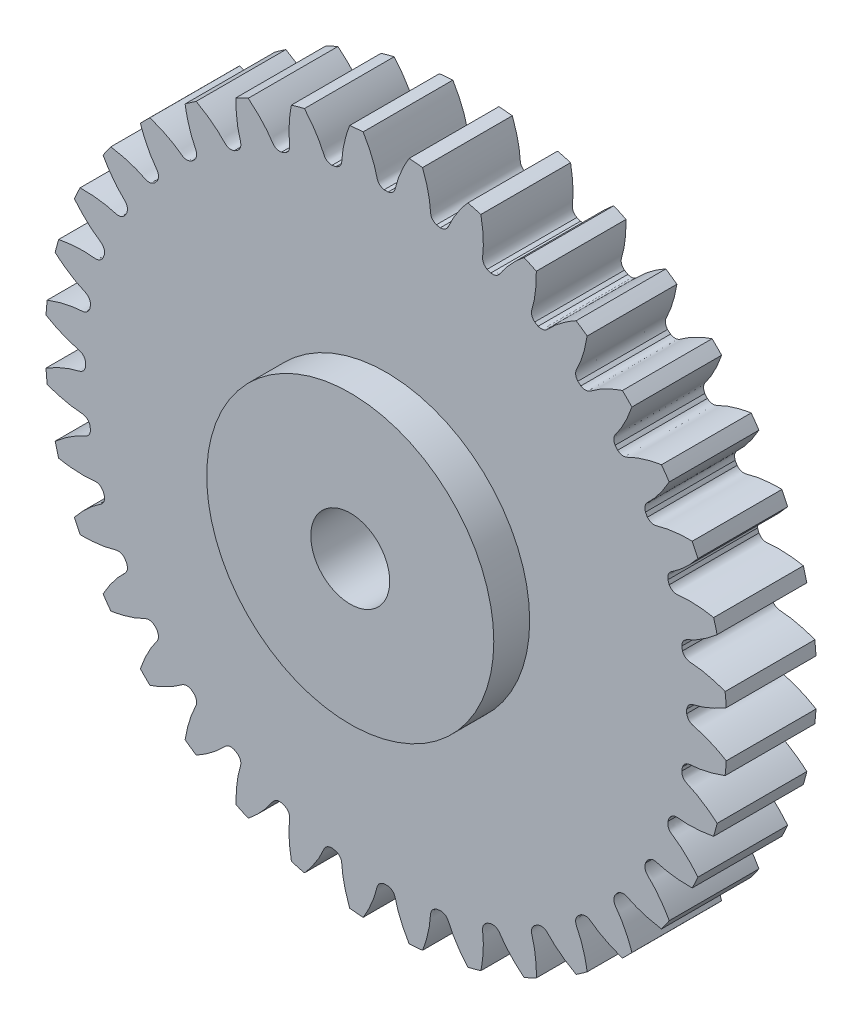
SolidWorks part; units mm, degrees
ref_plane "前视基准面" through (0, 0, 0) normal (0, 0, 1) x (1, 0, 0)
ref_plane "上视基准面" through (0, 0, 0) normal (0, 1, 0) x (1, 0, 0)
ref_plane "右视基准面" through (0, 0, 0) normal (1, 0, 0) x (0, 0, -1)
other "Configuration Table"
sketch "草图1" plane through (0, 0, 0) normal (0, 0, 1) x (1, 0, 0)
  circle A0 centre (0, 0) radius 9.5
extrude "凸台-拉伸1" add sketch "草图1" along normal blind 2.5
ref_axis "基准轴1" through (0, 0, 2.5) along (0, 0, -1)
sketch "草图2" plane through (0, 0, 0) normal (0, 0, 1) x (1, 0, 0)
  line L0 (0, 0) -> (0, 9.5) construction
  circle A0 centre (0, 0) radius 9.5 construction
  arc A1 (0.0549, 8.3748) -> (-0.0549, 8.3748) centre (0, 0) ccw
  arc A2 (1.757, 10.7884) -> (-1.757, 10.7884) centre (0, 0) ccw
  spline S0 degree 3 poles (0.0549, 8.3748) (0.235, 8.4152) (0.2505, 8.5493) (0.2882, 8.6914) (0.2997, 8.7319) (0.3131, 8.7753) (0.3284, 8.8217) (0.3457, 8.871) (0.3652, 8.9231) (0.3869, 8.9779) (0.4111, 9.0354) (0.4378, 9.0956) (0.4671, 9.1582) (0.4992, 9.2232) (0.5341, 9.2907) (0.5719, 9.3603) (0.6128, 9.4322) (0.6569, 9.5061) (0.7043, 9.582) (0.755, 9.6598) (0.8091, 9.7393) (0.8668, 9.8205) (0.9281, 9.9032) (0.9931, 9.9874) (1.0619, 10.0729) (1.1346, 10.1596) (1.2112, 10.2474) (1.2919, 10.3361) (1.3766, 10.4256) (1.4655, 10.5159) (1.5912, 10.6386) (1.6895, 10.7288) (1.757, 10.7884) knots 0 0 0 0 0.120371 0.133303 0.147364 0.162556 0.178878 0.19633 0.214913 0.234626 0.255469 0.277443 0.300547 0.324782 0.350146 0.376641 0.404267 0.433023 0.462909 0.493925 0.526072 0.559349 0.593757 0.629294 0.665963 0.703761 0.74269 0.782749 0.823939 0.866258 0.909709 1 1 1 1
  spline S1 degree 3 poles (-0.0549, 8.3748) (-0.235, 8.4152) (-0.2505, 8.5493) (-0.2882, 8.6914) (-0.2997, 8.7319) (-0.3131, 8.7753) (-0.3284, 8.8217) (-0.3457, 8.871) (-0.3652, 8.9231) (-0.3869, 8.9779) (-0.4111, 9.0354) (-0.4378, 9.0956) (-0.4671, 9.1582) (-0.4992, 9.2232) (-0.5341, 9.2907) (-0.5719, 9.3603) (-0.6128, 9.4322) (-0.6569, 9.5061) (-0.7043, 9.582) (-0.755, 9.6598) (-0.8091, 9.7393) (-0.8668, 9.8205) (-0.9281, 9.9032) (-0.9931, 9.9874) (-1.0619, 10.0729) (-1.1346, 10.1596) (-1.2112, 10.2474) (-1.2919, 10.3361) (-1.3766, 10.4256) (-1.4655, 10.5159) (-1.5912, 10.6386) (-1.6895, 10.7288) (-1.757, 10.7884) knots 0 0 0 0 0.120371 0.133303 0.147364 0.162556 0.178878 0.19633 0.214913 0.234626 0.255469 0.277443 0.300547 0.324782 0.350146 0.376641 0.404267 0.433023 0.462909 0.493925 0.526072 0.559349 0.593757 0.629294 0.665963 0.703761 0.74269 0.782749 0.823939 0.866258 0.909709 1 1 1 1
extrude "切除-拉伸1" cut sketch "草图2" along normal through all
pattern_circular "阵列(圆周)1" count 36 over 360 about axis through (0, 0, 2.5) along (0, 0, -1) of "切除-拉伸1"
sketch "草图3" plane through (0, 0, 0) normal (0, 0, 1) x (1, 0, 0)
  circle A0 centre (0, 0) radius 9 construction
  dimension "Dn" = 18
sketch "草图4" plane through (0, 0, 0) normal (0, 0, -1) x (-1, 0, 0)
  circle A0 centre (0, 0) radius 4
  dimension "D1" = 8
extrude "凸台-拉伸2" add sketch "草图4" against normal offset from surface (3.5 mm away) 1 up to face at (0, 0, 2.5) offset beyond the face yes
sketch "草图5" plane through (0, 0, 3.5) normal (0, 0, 1) x (1, 0, 0)
  circle A0 centre (0, 0) radius 1.1
  dimension "D1" = 2.2
extrude "切除-拉伸2" cut sketch "草图5" against normal up to next
